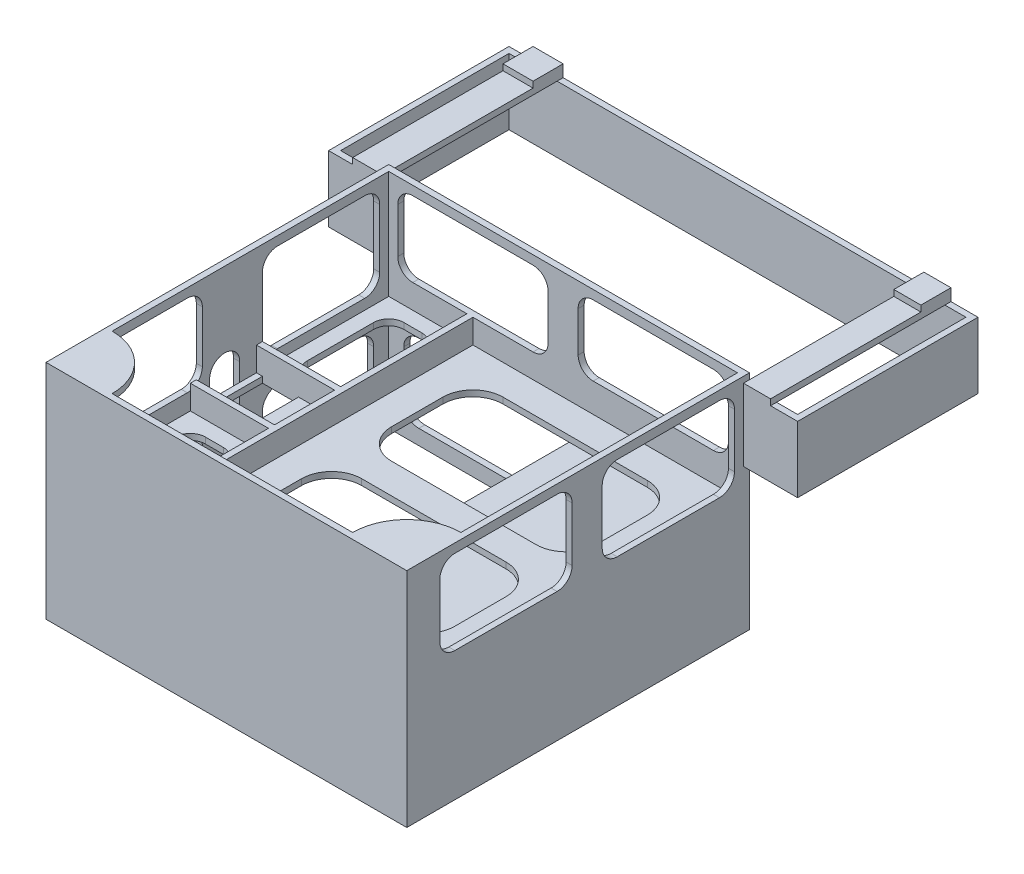
SolidWorks part; units mm, degrees
ref_plane "Front Plane" through (0, 0, 0) normal (0, 0, 1) x (1, 0, 0)
ref_plane "Top Plane" through (0, 0, 0) normal (0, 1, 0) x (1, 0, 0)
ref_plane "Right Plane" through (0, 0, 0) normal (1, 0, 0) x (0, 0, -1)
sketch "Sketch1" plane through (0, 0, 0) normal (0, 1, 0) x (1, 0, 0)
  line L1 (-113.8745, -60.9464) -> (-53.8745, -60.9464)
  line L2 (-113.8745, -60.9464) -> (-113.8745, -6.9464)
  line L3 (-113.8745, -6.9464) -> (-53.8745, -6.9464)
  line L4 (-53.8745, -60.9464) -> (-53.8745, -6.9464)
  dimension "D1" = 60
  dimension "D2" = 54
extrude "Boss-Extrude1" add sketch "Sketch1" along normal blind 38
sketch "Sketch2" plane through (0, 38, 0) normal (0, 1, 0) x (1, 0, 0)
  line L0 (-53.8745, -60.9464) -> (-53.8745, -6.9464) construction
  line L1 (-54.8745, -7.9464) -> (-98.8745, -7.9464)
  line L2 (-54.8745, -7.9464) -> (-54.8745, -59.9464)
  line L3 (-54.8745, -59.9464) -> (-98.8745, -59.9464)
  line L4 (-98.8745, -7.9464) -> (-98.8745, -59.9464)
  line L5 (-53.8745, -6.9464) -> (-113.8745, -6.9464) construction
  line L6 (-113.8745, -60.9464) -> (-53.8745, -60.9464) construction
  dimension "D1" = 1
  dimension "D2" = 1
  dimension "D3" = 1
  dimension "D4" = 44
extrude "Cut-Extrude1" cut sketch "Sketch2" against normal blind 19
sketch "Sketch3" plane through (0, 0, 0) normal (0, -1, 0) x (-1, 0, 0)
  line L0 (113.8745, -60.9464) -> (53.8745, -60.9464) construction
  line L1 (112.8745, -59.9464) -> (77.8745, -59.9464)
  line L2 (112.8745, -59.9464) -> (112.8745, -7.9464)
  line L3 (112.8745, -7.9464) -> (77.8745, -7.9464)
  line L4 (77.8745, -59.9464) -> (77.8745, -7.9464)
  line L5 (113.8745, -6.9464) -> (113.8745, -60.9464) construction
  line L6 (53.8745, -6.9464) -> (113.8745, -6.9464) construction
  dimension "D1" = 1
  dimension "D2" = 35
  dimension "D3" = 1
  dimension "D4" = 1
extrude "Cut-Extrude2" cut sketch "Sketch3" against normal blind 18
sketch "Sketch4" plane through (0, 18, 0) normal (0, -1, 0) x (-1, 0, 0)
  line L0 (77.8745, -59.9464) -> (112.8745, -59.9464) construction
  line L1 (111.8745, -39.9464) -> (105.8745, -39.9464)
  line L2 (111.8745, -39.9464) -> (111.8745, -29.9464)
  line L3 (111.8745, -29.9464) -> (105.8745, -29.9464)
  line L4 (105.8745, -39.9464) -> (105.8745, -29.9464)
  line L5 (112.8745, -7.9464) -> (77.8745, -7.9464) construction
  line L6 (112.8745, -59.9464) -> (112.8745, -7.9464) construction
  dimension "D1" = 20
  dimension "D2" = 22
  dimension "D3" = 1
  dimension "D4" = 6
extrude "Cut-Extrude3" cut sketch "Sketch4" against normal blind 38
sketch "Sketch5" plane through (0, 38, 0) normal (0, 1, 0) x (1, 0, 0)
  line L0 (-53.8745, -6.9464) -> (-113.8745, -6.9464) construction
  line L1 (-98.8745, -59.9464) -> (-112.8745, -59.9464)
  line L2 (-98.8745, -59.9464) -> (-98.8745, -7.9464)
  line L3 (-98.8745, -7.9464) -> (-112.8745, -7.9464)
  line L4 (-112.8745, -59.9464) -> (-112.8745, -7.9464)
  line L5 (-113.8745, -6.9464) -> (-113.8745, -60.9464) construction
  dimension "D1" = 1
  dimension "D2" = 1
extrude "Cut-Extrude5" cut sketch "Sketch5" against normal blind 15
sketch "Sketch6" plane through (0, 23, 0) normal (0, 1, 0) x (1, 0, 0)
  line L0 (-112.8745, -59.9464) -> (-98.8745, -59.9464) construction
  line L1 (-112.8745, -7.9464) -> (-99.8745, -7.9464)
  line L2 (-112.8745, -7.9464) -> (-112.8745, -59.9464)
  line L3 (-112.8745, -59.9464) -> (-99.8745, -59.9464)
  line L4 (-99.8745, -7.9464) -> (-99.8745, -59.9464)
  line L5 (-98.8745, -59.9464) -> (-98.8745, -7.9464) construction
  dimension "D1" = 1
extrude "Cut-Extrude6" cut sketch "Sketch6" against normal blind 4
sketch "Sketch8" plane through (0, 0, 0) normal (0, -1, 0) x (-1, 0, 0)
  line L0 (53.8745, -60.9464) -> (53.8745, -6.9464) construction
  line L1 (72.3745, -11.4464) -> (58.3745, -11.4464)
  line L2 (72.3745, -11.4464) -> (72.3745, -23.9464)
  line L3 (72.3745, -23.9464) -> (58.3745, -23.9464)
  line L4 (58.3745, -11.4464) -> (58.3745, -23.9464)
  line L6 (53.8745, -6.9464) -> (113.8745, -6.9464) construction
  dimension "D1" = 14
  dimension "D2" = 12.5
  dimension "D3" = 4.5
  dimension "D4" = 4.5
extrude "Cut-Extrude7" cut sketch "Sketch8" against normal blind 6
sketch "Sketch10" plane through (-72.3745, 0, 0) normal (1, 0, 0) x (0, 0, -1)
  line L0 (-11.4464, 6) -> (-11.4464, 0) construction
  line L1 (-23.9464, 6) -> (-11.4464, 6)
  line L2 (-23.9464, 6) -> (-23.9464, 1)
  line L3 (-23.9464, 1) -> (-11.4464, 1)
  line L4 (-11.4464, 6) -> (-11.4464, 1)
  line L5 (-23.9464, 0) -> (-11.4464, 0) construction
  dimension "D1" = 1
extrude "Cut-Extrude8" cut sketch "Sketch10" against normal blind 6
sketch "Sketch11" plane through (0, 0, 0) normal (0, -1, 0) x (1, 0, 0)
  line L0 (-113.8745, 60.9464) -> (-53.8745, 60.9464) construction
  line L1 (-68.3745, 50.9464) -> (-63.8745, 50.9464)
  line L2 (-68.3745, 50.9464) -> (-68.3745, 45.9464)
  line L3 (-68.3745, 45.9464) -> (-63.8745, 45.9464)
  line L4 (-63.8745, 50.9464) -> (-63.8745, 45.9464)
  line L5 (-53.8745, 60.9464) -> (-53.8745, 6.9464) construction
  dimension "D1" = 4.5
  dimension "D2" = 5
  dimension "D3" = 10
  dimension "D4" = 10
extrude "Cut-Extrude9" cut sketch "Sketch11" against normal blind 3
sketch "Sketch12" plane through (-68.3745, 0, 0) normal (1, 0, 0) x (0, 0, -1)
  line L0 (-50.9464, 3) -> (-50.9464, 0) construction
  line L1 (-45.9464, 3) -> (-50.9464, 3)
  line L2 (-45.9464, 3) -> (-45.9464, 1)
  line L3 (-45.9464, 1) -> (-50.9464, 1)
  line L4 (-50.9464, 3) -> (-50.9464, 1)
  line L5 (-50.9464, 0) -> (-45.9464, 0) construction
  dimension "D1" = 1
extrude "Cut-Extrude10" cut sketch "Sketch12" against normal blind 13
sketch "Sketch13" plane through (-113.8745, 0, 0) normal (-1, 0, 0) x (0, 0, 1)
  line L0 (35.233, 15) -> (35.233, 22) construction
  line L1 (32.733, 15) -> (32.733, 22)
  line L2 (37.733, 15) -> (37.733, 22)
  line L3 (59.9464, 18) -> (7.9464, 18) construction
  line L4 (39.9464, 19) -> (29.9464, 19) construction
  arc A0 (32.733, 15) -> (37.733, 15) centre (35.233, 15) ccw
  arc A1 (37.733, 22) -> (32.733, 22) centre (35.233, 22) ccw
  point P2 (35.233, 18.5)
  dimension "D1" = 3
  dimension "D2" = 3
  dimension "D3" = 2.5
extrude "Cut-Extrude11" cut sketch "Sketch13" against normal blind 1
sketch "Sketch14" plane through (0, 19, 0) normal (0, 1, 0) x (1, 0, 0)
  line L0 (-99.8745, -59.9464) -> (-99.8745, -7.9464) construction
  line L1 (-112.8745, -40.9464) -> (-99.8745, -40.9464)
  line L2 (-112.8745, -40.9464) -> (-112.8745, -39.9464)
  line L3 (-112.8745, -39.9464) -> (-99.8745, -39.9464)
  line L4 (-99.8745, -40.9464) -> (-99.8745, -39.9464)
  line L5 (-112.8745, -37.733) -> (-112.8745, -59.9464) construction
  line L6 (-105.8745, -39.9464) -> (-111.8745, -39.9464) construction
  dimension "D1" = 0
  dimension "D2" = 1
  dimension "D3" = 0
extrude "Boss-Extrude2" add sketch "Sketch14" along normal blind 4
sketch "Sketch15" plane through (0, 19, 0) normal (0, 1, 0) x (1, 0, 0)
  line L0 (-112.8745, -7.9464) -> (-112.8745, -32.733) construction
  line L1 (-112.8745, -29.9464) -> (-99.8745, -29.9464)
  line L2 (-112.8745, -29.9464) -> (-112.8745, -28.9464)
  line L3 (-112.8745, -28.9464) -> (-99.8745, -28.9464)
  line L4 (-99.8745, -29.9464) -> (-99.8745, -28.9464)
  line L5 (-99.8745, -39.9464) -> (-99.8745, -7.9464) construction
  line L6 (-111.8745, -29.9464) -> (-105.8745, -29.9464) construction
  dimension "D1" = 0
  dimension "D2" = 1
extrude "Boss-Extrude3" add sketch "Sketch15" along normal blind 4
sketch "Sketch16" plane through (0, 19, 0) normal (0, 1, 0) x (1, 0, 0)
  line L0 (-98.8745, -59.9464) -> (-54.8745, -59.9464) construction
  line L1 (-64.8745, -54.9464) -> (-88.8745, -54.9464)
  line L2 (-59.8745, -49.9464) -> (-59.8745, -41.4464)
  line L3 (-64.8745, -36.4464) -> (-88.8745, -36.4464)
  line L4 (-93.8745, -49.9464) -> (-93.8745, -41.4464)
  line L5 (-88.8745, -31.4464) -> (-64.8745, -31.4464)
  line L6 (-93.8745, -26.4464) -> (-93.8745, -17.9464)
  line L7 (-88.8745, -12.9464) -> (-64.8745, -12.9464)
  line L8 (-59.8745, -26.4464) -> (-59.8745, -17.9464)
  line L9 (-54.8745, -59.9464) -> (-54.8745, -7.9464) construction
  line L10 (-98.8745, -7.9464) -> (-98.8745, -59.9464) construction
  line L11 (-54.8745, -7.9464) -> (-98.8745, -7.9464) construction
  arc A0 (-64.8745, -31.4464) -> (-59.8745, -26.4464) centre (-64.8745, -26.4464) ccw
  arc A1 (-64.8745, -12.9464) -> (-59.8745, -17.9464) centre (-64.8745, -17.9464) cw
  arc A2 (-93.8745, -17.9464) -> (-88.8745, -12.9464) centre (-88.8745, -17.9464) cw
  arc A3 (-88.8745, -31.4464) -> (-93.8745, -26.4464) centre (-88.8745, -26.4464) cw
  arc A4 (-88.8745, -54.9464) -> (-93.8745, -49.9464) centre (-88.8745, -49.9464) cw
  arc A5 (-88.8745, -36.4464) -> (-93.8745, -41.4464) centre (-88.8745, -41.4464) ccw
  arc A6 (-59.8745, -41.4464) -> (-64.8745, -36.4464) centre (-64.8745, -41.4464) ccw
  arc A7 (-64.8745, -54.9464) -> (-59.8745, -49.9464) centre (-64.8745, -49.9464) ccw
  point P22 (-93.8745, -12.9464)
  point P25 (-93.8745, -31.4464)
  dimension "D9" = 5
  dimension "D1" = 5
  dimension "D2" = 5
  dimension "D3" = 5
  dimension "D4" = 5
  dimension "D5" = 5
  dimension "D6" = 5
  dimension "D7" = 5
  dimension "D8" = 18.5
extrude "Cut-Extrude12" cut sketch "Sketch16" against normal blind 1
sketch "Sketch17" plane through (0, 19, 0) normal (0, 1, 0) x (1, 0, 0)
  line L0 (-112.8745, -40.9464) -> (-112.8745, -59.9464) construction
  line L1 (-104.8745, -57.4464) -> (-107.8745, -57.4464)
  line L2 (-102.3745, -54.9464) -> (-102.3745, -45.9464)
  line L3 (-104.8745, -43.4464) -> (-107.8745, -43.4464)
  line L4 (-110.3745, -54.9464) -> (-110.3745, -45.9464)
  line L5 (-104.8745, -26.4464) -> (-107.8745, -26.4464)
  line L6 (-102.3745, -23.9464) -> (-102.3745, -12.9464)
  line L7 (-104.8745, -10.4464) -> (-107.8745, -10.4464)
  line L8 (-110.3745, -23.9464) -> (-110.3745, -12.9464)
  line L9 (-99.8745, -59.9464) -> (-99.8745, -40.9464) construction
  line L10 (-112.8745, -40.9464) -> (-99.8745, -40.9464) construction
  line L11 (-112.8745, -59.9464) -> (-99.8745, -59.9464) construction
  line L12 (-99.8745, -28.9464) -> (-112.8745, -28.9464) construction
  line L13 (-112.8745, -7.9464) -> (-112.8745, -28.9464) construction
  line L14 (-99.8745, -28.9464) -> (-99.8745, -7.9464) construction
  line L15 (-99.8745, -7.9464) -> (-112.8745, -7.9464) construction
  arc A0 (-102.3745, -12.9464) -> (-104.8745, -10.4464) centre (-104.8745, -12.9464) ccw
  arc A1 (-107.8745, -10.4464) -> (-110.3745, -12.9464) centre (-107.8745, -12.9464) ccw
  arc A2 (-107.8745, -26.4464) -> (-110.3745, -23.9464) centre (-107.8745, -23.9464) cw
  arc A3 (-104.8745, -26.4464) -> (-102.3745, -23.9464) centre (-104.8745, -23.9464) ccw
  arc A4 (-102.3745, -45.9464) -> (-104.8745, -43.4464) centre (-104.8745, -45.9464) ccw
  arc A5 (-107.8745, -43.4464) -> (-110.3745, -45.9464) centre (-107.8745, -45.9464) ccw
  arc A6 (-107.8745, -57.4464) -> (-110.3745, -54.9464) centre (-107.8745, -54.9464) cw
  arc A7 (-104.8745, -57.4464) -> (-102.3745, -54.9464) centre (-104.8745, -54.9464) ccw
  dimension "D9" = 2.5
  dimension "D1" = 2.5
  dimension "D2" = 2.5
  dimension "D3" = 2.5
  dimension "D4" = 2.5
  dimension "D5" = 2.5
  dimension "D6" = 2.5
  dimension "D7" = 2.5
  dimension "D8" = 2.5
extrude "Cut-Extrude13" cut sketch "Sketch17" against normal blind 1
sketch "Sketch18" plane through (-53.8745, 0, 0) normal (1, 0, 0) x (0, 0, -1)
  line L0 (-60.9464, 38) -> (-6.9464, 38) construction
  line L1 (-55.9464, 35.5) -> (-38.9464, 35.5)
  line L2 (-58.4464, 33) -> (-58.4464, 24)
  line L3 (-55.9464, 21.5) -> (-38.9464, 21.5)
  line L4 (-36.4464, 33) -> (-36.4464, 24)
  line L5 (-28.9464, 35.5) -> (-11.9464, 35.5)
  line L6 (-31.4464, 33) -> (-31.4464, 24)
  line L7 (-28.9464, 21.5) -> (-11.9464, 21.5)
  line L8 (-9.4464, 33) -> (-9.4464, 24)
  line L9 (-60.9464, 38) -> (-60.9464, 0) construction
  line L10 (-6.9464, 38) -> (-6.9464, 0) construction
  line L11 (-59.9464, 19) -> (-7.9464, 19) construction
  arc A0 (-31.4464, 24) -> (-28.9464, 21.5) centre (-28.9464, 24) ccw
  arc A1 (-11.9464, 21.5) -> (-9.4464, 24) centre (-11.9464, 24) ccw
  arc A2 (-11.9464, 35.5) -> (-9.4464, 33) centre (-11.9464, 33) cw
  arc A3 (-28.9464, 35.5) -> (-31.4464, 33) centre (-28.9464, 33) ccw
  arc A4 (-58.4464, 24) -> (-55.9464, 21.5) centre (-55.9464, 24) ccw
  arc A5 (-38.9464, 21.5) -> (-36.4464, 24) centre (-38.9464, 24) ccw
  arc A6 (-38.9464, 35.5) -> (-36.4464, 33) centre (-38.9464, 33) cw
  arc A7 (-55.9464, 35.5) -> (-58.4464, 33) centre (-55.9464, 33) ccw
  point P26 (-58.4464, 21.5)
  point P29 (-36.4464, 21.5)
  dimension "D9" = 2.5
  dimension "D1" = 2.5
  dimension "D2" = 2.5
  dimension "D3" = 2.5
  dimension "D4" = 2.5
  dimension "D5" = 5
  dimension "D6" = 22
  dimension "D7" = 2.5
  dimension "D8" = 2.5
extrude "Cut-Extrude14" cut sketch "Sketch18" against normal blind 1
sketch "Sketch19" plane through (0, 0, 6.9464) normal (0, 0, -1) x (-1, 0, 0)
  line L0 (53.8745, 38) -> (113.8745, 38) construction
  line L1 (58.8745, 35.5) -> (78.8745, 35.5)
  line L2 (56.3745, 33) -> (56.3745, 26.3041)
  line L3 (58.8745, 23.8041) -> (78.8745, 23.8041)
  line L4 (81.3745, 33) -> (81.3745, 26.3041)
  line L5 (88.8745, 35.5) -> (108.8745, 35.5)
  line L6 (86.3745, 33) -> (86.3745, 25.5)
  line L7 (88.8745, 23) -> (108.8745, 23)
  line L8 (111.3745, 33) -> (111.3745, 25.5)
  line L9 (113.8745, 38) -> (113.8745, 0) construction
  line L10 (53.8745, 38) -> (53.8745, 0) construction
  arc A0 (108.8745, 23) -> (111.3745, 25.5) centre (108.8745, 25.5) ccw
  arc A1 (108.8745, 35.5) -> (111.3745, 33) centre (108.8745, 33) cw
  arc A2 (88.8745, 35.5) -> (86.3745, 33) centre (88.8745, 33) ccw
  arc A3 (86.3745, 25.5) -> (88.8745, 23) centre (88.8745, 25.5) ccw
  arc A4 (78.8745, 23.8041) -> (81.3745, 26.3041) centre (78.8745, 26.3041) ccw
  arc A5 (78.8745, 35.5) -> (81.3745, 33) centre (78.8745, 33) cw
  arc A6 (56.3745, 26.3041) -> (58.8745, 23.8041) centre (58.8745, 26.3041) ccw
  arc A7 (58.8745, 35.5) -> (56.3745, 33) centre (58.8745, 33) ccw
  point P17 (111.3745, 23)
  point P24 (86.3745, 23)
  dimension "D8" = 2.5
  dimension "D1" = 2.5
  dimension "D2" = 2.5
  dimension "D3" = 2.5
  dimension "D4" = 2.5
  dimension "D5" = 5
  dimension "D6" = 25
  dimension "D7" = 0
extrude "Cut-Extrude15" cut sketch "Sketch19" against normal blind 60
sketch "Sketch20" plane through (-113.8745, 0, 0) normal (-1, 0, 0) x (0, 0, 1)
  line L0 (59.9464, 38) -> (7.9464, 38) construction
  line L1 (11.9464, 35.5) -> (26.4464, 35.5)
  line L2 (9.4464, 33) -> (9.4464, 23.222)
  line L3 (11.9464, 20.722) -> (26.4464, 20.722)
  line L4 (28.9464, 33) -> (28.9464, 23.222)
  line L5 (41.4464, 35.5) -> (55.9464, 35.5)
  line L6 (38.9464, 33) -> (38.9464, 24.3756)
  line L7 (41.4464, 21.8756) -> (55.9464, 21.8756)
  line L8 (58.4464, 33) -> (58.4464, 24.3756)
  line L9 (6.9464, 38) -> (6.9464, 0) construction
  line L10 (60.9464, 38) -> (60.9464, 0) construction
  line L11 (6.9464, 38) -> (60.9464, 38) construction
  arc A0 (38.9464, 24.3756) -> (41.4464, 21.8756) centre (41.4464, 24.3756) ccw
  arc A1 (55.9464, 21.8756) -> (58.4464, 24.3756) centre (55.9464, 24.3756) ccw
  arc A2 (55.9464, 35.5) -> (58.4464, 33) centre (55.9464, 33) cw
  arc A3 (41.4464, 35.5) -> (38.9464, 33) centre (41.4464, 33) ccw
  arc A4 (9.4464, 23.222) -> (11.9464, 20.722) centre (11.9464, 23.222) ccw
  arc A5 (26.4464, 20.722) -> (28.9464, 23.222) centre (26.4464, 23.222) ccw
  arc A6 (26.4464, 35.5) -> (28.9464, 33) centre (26.4464, 33) cw
  arc A7 (11.9464, 35.5) -> (9.4464, 33) centre (11.9464, 33) ccw
  point P18 (38.9464, 21.8756)
  point P21 (58.4464, 21.8756)
  dimension "D7" = 2.5
  dimension "D1" = 2.5
  dimension "D2" = 2.5
  dimension "D3" = 10
  dimension "D4" = 2.5
  dimension "D5" = 2.5
  dimension "D6" = 19.5
extrude "Cut-Extrude16" cut sketch "Sketch20" against normal blind 1
sketch "Sketch21" plane through (0, 0, 59.9464) normal (0, 0, -1) x (-1, 0, 0)
  line L0 (77.8745, 0) -> (112.8745, 0) construction
  line L1 (107.8745, 2.5) -> (82.8745, 2.5)
  line L2 (110.3745, 5) -> (110.3745, 13)
  line L3 (107.8745, 15.5) -> (82.8745, 15.5)
  line L4 (80.3745, 5) -> (80.3745, 13)
  line L5 (77.8745, 18) -> (77.8745, 0) construction
  line L6 (112.8745, 18) -> (112.8745, 0) construction
  line L7 (77.8745, 18) -> (112.8745, 18) construction
  arc A0 (110.3745, 13) -> (107.8745, 15.5) centre (107.8745, 13) ccw
  arc A1 (82.8745, 15.5) -> (80.3745, 13) centre (82.8745, 13) ccw
  arc A2 (82.8745, 2.5) -> (80.3745, 5) centre (82.8745, 5) cw
  arc A3 (107.8745, 2.5) -> (110.3745, 5) centre (107.8745, 5) ccw
  dimension "D5" = 2.5
  dimension "D1" = 2.5
  dimension "D2" = 2.5
  dimension "D3" = 2.5
  dimension "D4" = 2.5
extrude "Cut-Extrude17" cut sketch "Sketch21" along normal blind 100 and the other way blind 10
sketch "Sketch22" plane through (-112.8745, 0, 0) normal (1, 0, 0) x (0, 0, -1)
  line L0 (-59.9464, 0) -> (-7.9464, 0) construction
  line L1 (-12.9464, 2.5) -> (-26.4464, 2.5)
  line L2 (-10.4464, 5) -> (-10.4464, 13)
  line L3 (-12.9464, 15.5) -> (-26.4464, 15.5)
  line L4 (-28.9464, 5) -> (-28.9464, 13)
  line L5 (-41.4464, 2.5) -> (-54.9464, 2.5)
  line L6 (-38.9464, 5) -> (-38.9464, 13)
  line L7 (-41.4464, 15.5) -> (-54.9464, 15.5)
  line L8 (-57.4464, 5) -> (-57.4464, 13)
  line L9 (-7.9464, 18) -> (-7.9464, 0) construction
  line L10 (-32.733, 18) -> (-7.9464, 18) construction
  line L11 (-59.9464, 18) -> (-37.733, 18) construction
  line L12 (-59.9464, 18) -> (-59.9464, 0) construction
  arc A0 (-38.9464, 13) -> (-41.4464, 15.5) centre (-41.4464, 13) ccw
  arc A1 (-54.9464, 15.5) -> (-57.4464, 13) centre (-54.9464, 13) ccw
  arc A2 (-54.9464, 2.5) -> (-57.4464, 5) centre (-54.9464, 5) cw
  arc A3 (-41.4464, 2.5) -> (-38.9464, 5) centre (-41.4464, 5) ccw
  arc A4 (-26.4464, 2.5) -> (-28.9464, 5) centre (-26.4464, 5) cw
  arc A5 (-26.4464, 15.5) -> (-28.9464, 13) centre (-26.4464, 13) ccw
  arc A6 (-10.4464, 13) -> (-12.9464, 15.5) centre (-12.9464, 13) ccw
  arc A7 (-12.9464, 2.5) -> (-10.4464, 5) centre (-12.9464, 5) ccw
  point P30 (-28.9464, 15.5)
  point P33 (-10.4464, 15.5)
  dimension "D9" = 2.5
  dimension "D1" = 2.5
  dimension "D2" = 10
  dimension "D3" = 2.5
  dimension "D4" = 2.5
  dimension "D5" = 2.5
  dimension "D6" = 2.5
  dimension "D7" = 2.5
  dimension "D8" = 18.5
extrude "Cut-Extrude18" cut sketch "Sketch22" against normal blind 10
sketch "Sketch23" plane through (0, 38, 0) normal (0, 1, 0) x (1, 0, 0)
  line L1 (-112.8745, -59.9464) -> (-54.8745, -59.9464)
  line L2 (-112.8745, -59.9464) -> (-112.8745, -7.9464)
  line L3 (-112.8745, -7.9464) -> (-54.8745, -7.9464)
  line L4 (-54.8745, -59.9464) -> (-54.8745, -7.9464)
extrude "Boss-Extrude4" add sketch "Sketch23" against normal blind 1
sketch "Sketch24" plane through (0, 38, 0) normal (0, 1, 0) x (1, 0, 0)
  line L0 (-113.8745, -6.9464) -> (-113.8745, -60.9464) construction
  line L1 (-113.8745, -50.9464) -> (-53.8745, -50.9464)
  line L2 (-113.8745, -50.9464) -> (-113.8745, -16.9464)
  line L3 (-113.8745, -16.9464) -> (-53.8745, -16.9464)
  line L4 (-53.8745, -50.9464) -> (-53.8745, -16.9464)
  line L5 (-53.8745, -60.9464) -> (-53.8745, -6.9464) construction
  line L6 (-53.8745, -6.9464) -> (-113.8745, -6.9464) construction
  line L7 (-103.8745, -6.9464) -> (-63.8745, -6.9464)
  line L8 (-103.8745, -6.9464) -> (-103.8745, -60.9464)
  line L9 (-103.8745, -60.9464) -> (-63.8745, -60.9464)
  line L10 (-63.8745, -6.9464) -> (-63.8745, -60.9464)
  line L11 (-113.8745, -60.9464) -> (-53.8745, -60.9464) construction
  line L12 (-58.8745, -60.9464) -> (-56.3745, -60.9464) construction
  line M5 (-113.8745, -6.9464) -> (-113.8745, -60.9464)
  line M6 (-113.8745, -60.9464) -> (-53.8745, -60.9464)
  line M7 (-53.8745, -60.9464) -> (-53.8745, -6.9464)
  line M8 (-53.8745, -6.9464) -> (-113.8745, -6.9464)
  dimension "D1" = 10
  dimension "D2" = 10
  dimension "D3" = 10
  dimension "D4" = 10
extrude "Cut-Extrude20" cut sketch "Sketch24" against normal blind 1 contours L10 L1 L8 M6 | L3 L10 L1 M7 | L10 L8 L3 M8 | L10 L3 L8 L1 | L8 L3 L1 M5
fillet "Fillet1" radius 9 3 edges at (-103.8745, 37, 55.4464) (-108.3745, 37, 50.9464) (-103.8745, 37.5, 50.9464)
fillet "Fillet2" radius 9 3 edges at (-63.8745, 37, 12.4464) (-59.3745, 37, 16.9464) (-63.8745, 37.5, 16.9464)
fillet "Fillet3" radius 9 3 edges at (-63.8745, 37, 55.4464) (-63.8745, 37.5, 50.9464) (-59.3745, 37, 50.9464)
fillet "Fillet4" radius 9 3 edges at (-108.3745, 37, 16.9464) (-103.8745, 37, 12.4464) (-103.8745, 37.5, 16.9464)
sketch "Sketch27" plane through (0, 0, 6.9464) normal (0, 0, -1) x (-1, 0, 0)
  line L0 (53.8745, 38) -> (53.8745, 0) construction
  line L1 (53.8745, 24) -> (43.8745, 24)
  line L2 (53.8745, 24) -> (53.8745, 35)
  line L3 (53.8745, 35) -> (43.8745, 35)
  line L4 (43.8745, 24) -> (43.8745, 35)
  line L5 (113.8745, 38) -> (113.8745, 0) construction
  line L6 (113.8745, 24) -> (123.8745, 24)
  line L7 (113.8745, 24) -> (113.8745, 35)
  line L8 (113.8745, 35) -> (123.8745, 35)
  line L9 (123.8745, 24) -> (123.8745, 35)
  line L10 (63.8745, 37) -> (103.8745, 37) construction
  dimension "D1" = 2
  dimension "D2" = 2
  dimension "D3" = 80
  dimension "D4" = 10
  dimension "D5" = 11
  dimension "D6" = 11
extrude "Boss-Extrude10" add sketch "Sketch27" against normal blind 1
sketch "Sketch31" plane through (0, 0, 6.9464) normal (0, 0, -1) x (-1, 0, 0)
  line L0 (43.8745, 24) -> (53.8745, 24) construction
  line L1 (43.8745, 24) -> (44.8745, 24)
  line L2 (43.8745, 24) -> (43.8745, 35)
  line L3 (43.8745, 35) -> (44.8745, 35)
  line L4 (44.8745, 24) -> (44.8745, 35)
  line L5 (53.8745, 35) -> (43.8745, 35) construction
  line L6 (123.8745, 35) -> (113.8745, 35) construction
  line L7 (122.8745, 35) -> (123.8745, 35)
  line L8 (122.8745, 35) -> (122.8745, 24)
  line L9 (122.8745, 24) -> (123.8745, 24)
  line L10 (123.8745, 35) -> (123.8745, 24)
  dimension "D1" = 1
  dimension "D2" = 1
extrude "Boss-Extrude12" add sketch "Sketch31" along normal blind 29
sketch "Sketch33" plane through (-44.8745, 0, 0) normal (-1, 0, 0) x (0, 0, 1)
  line L0 (-22.0536, 24) -> (6.9464, 24) construction
  line L1 (-22.0536, 35) -> (-21.0536, 35)
  line L2 (-22.0536, 35) -> (-22.0536, 24)
  line L3 (-22.0536, 24) -> (-21.0536, 24)
  line L4 (-21.0536, 35) -> (-21.0536, 24)
  dimension "D1" = 1
extrude "Boss-Extrude13" add sketch "Sketch33" along normal blind 78
sketch "Sketch34" plane through (0, 35, 0) normal (0, 1, 0) x (1, 0, 0)
  line L0 (-123.8745, -7.9464) -> (-113.8745, -7.9464) construction
  line L1 (-123.8745, 22.0536) -> (-43.8745, 22.0536) construction
  line L2 (-118.8745, -7.9464) -> (-113.8745, -7.9464)
  line L3 (-118.8745, -7.9464) -> (-118.8745, 22.0536)
  line L4 (-118.8745, 22.0536) -> (-113.8745, 22.0536)
  line L5 (-113.8745, -7.9464) -> (-113.8745, 22.0536)
  line L7 (-53.8745, -7.9464) -> (-49.3745, -7.9464)
  line L8 (-53.8745, -7.9464) -> (-53.8745, 22.0536)
  line L9 (-53.8745, 22.0536) -> (-49.3745, 22.0536)
  line L10 (-49.3745, -7.9464) -> (-49.3745, 22.0536)
extrude "Boss-Extrude14" add sketch "Sketch34" along normal blind 1
sketch "Sketch35" plane through (-122.8745, 0, 0) normal (1, 0, 0) x (0, 0, -1)
  line L0 (21.0536, 24) -> (-6.9464, 24) construction
  line L1 (21.0536, 24) -> (-6.9464, 24)
  line L2 (21.0536, 24) -> (21.0536, 35)
  line L3 (21.0536, 35) -> (-6.9464, 35)
  line L4 (-6.9464, 24) -> (-6.9464, 35)
extrude "Boss-Extrude15" add sketch "Sketch35" along normal blind 1
sketch "Sketch37" plane through (-123.8745, 0, 0) normal (-1, 0, 0) x (0, 0, 1)
  line L1 (7.9464, 35) -> (-22.0536, 35)
  line L2 (7.9464, 35) -> (7.9464, 24)
  line L3 (7.9464, 24) -> (-22.0536, 24)
  line L4 (-22.0536, 35) -> (-22.0536, 24)
  point P4 (-10.4832, 37.0116)
extrude "Cut-Extrude21" cut sketch "Sketch37" against normal blind 1
sketch "Sketch38" plane through (-44.8745, 0, 0) normal (-1, 0, 0) x (0, 0, 1)
  line L1 (6.9464, 35) -> (-21.0536, 35)
  line L2 (6.9464, 35) -> (6.9464, 24)
  line L3 (6.9464, 24) -> (-21.0536, 24)
  line L4 (-21.0536, 35) -> (-21.0536, 24)
extrude "Boss-Extrude16" add sketch "Sketch38" along normal blind 1
sketch "Sketch39" plane through (-43.8745, 0, 0) normal (1, 0, 0) x (0, 0, -1)
  line L1 (-7.9464, 24) -> (22.0536, 24)
  line L2 (-7.9464, 24) -> (-7.9464, 35)
  line L3 (-7.9464, 35) -> (22.0536, 35)
  line L4 (22.0536, 24) -> (22.0536, 35)
  point P4 (10.6616, 17.0387)
extrude "Cut-Extrude22" cut sketch "Sketch39" against normal blind 1
sketch "Sketch40" plane through (0, 0, 60.9464) normal (0, 0, 1) x (1, 0, 0)
  line L0 (-113.8745, 38) -> (-113.8745, 0) construction
  line L1 (-53.8745, 0) -> (-113.8745, 0)
  line L2 (-53.8745, 0) -> (-53.8745, 37)
  line L3 (-53.8745, 37) -> (-113.8745, 37)
  line L4 (-113.8745, 0) -> (-113.8745, 37)
  dimension "D1" = 37
extrude "Boss-Extrude17" add sketch "Sketch40" along normal blind 3
sketch "Sketch41" plane through (0, 0, 59.9464) normal (0, 0, -1) x (-1, 0, 0)
  line L1 (112.8745, 0) -> (77.8745, 0)
  line L2 (112.8745, 0) -> (112.8745, 18)
  line L3 (112.8745, 18) -> (77.8745, 18)
  line L4 (77.8745, 0) -> (77.8745, 18)
  point P4 (75.1365, 25.7269)
extrude "Cut-Extrude23" cut sketch "Sketch41" against normal blind 3
sketch "Sketch42" plane through (0, 0, 59.9464) normal (0, 0, -1) x (-1, 0, 0)
  line L0 (98.8745, 19) -> (54.8745, 19) construction
  line L1 (98.8745, 19) -> (54.8745, 19)
  line L2 (98.8745, 19) -> (98.8745, 37)
  line L3 (98.8745, 37) -> (54.8745, 37)
  line L4 (54.8745, 19) -> (54.8745, 37)
  line L5 (54.8745, 19) -> (54.8745, 37) construction
  point P8 (53.8849, 38.6439)
  point P9 (85.8975, 35.987)
extrude "Cut-Extrude24" cut sketch "Sketch42" against normal blind 3
sketch "Sketch44" plane through (0, 0, 59.9464) normal (0, 0, -1) x (-1, 0, 0)
  line L0 (103.8745, 37) -> (98.8745, 37) construction
  line L1 (112.8745, 19) -> (99.8745, 19)
  line L2 (112.8745, 19) -> (112.8745, 37)
  line L3 (112.8745, 37) -> (99.8745, 37)
  line L4 (99.8745, 19) -> (99.8745, 37)
  point P7 (100.7339, 25.4341)
  dimension "D1" = 13
extrude "Cut-Extrude25" cut sketch "Sketch44" against normal blind 3
sketch "Sketch45" plane through (-98.8745, 0, 0) normal (1, 0, 0) x (0, 0, -1)
  line L0 (-62.9464, 37) -> (-59.9464, 37) construction
  line L1 (-62.9464, 37) -> (-59.9464, 37)
  line L2 (-62.9464, 37) -> (-62.9464, 23)
  line L3 (-62.9464, 23) -> (-59.9464, 23)
  line L4 (-59.9464, 37) -> (-59.9464, 23)
  line L5 (-60.9464, 23) -> (-7.9464, 23) construction
  point P8 (-55.7959, 40.5595)
extrude "Cut-Extrude26" cut sketch "Sketch45" against normal blind 3
sketch "Sketch47" plane through (0, 38, 0) normal (0, 1, 0) x (1, 0, 0)
  line L1 (-113.8745, -6.9464) -> (-53.8745, -6.9464)
  line L2 (-113.8745, -6.9464) -> (-113.8745, -16.9464)
  line L3 (-113.8745, -16.9464) -> (-53.8745, -16.9464)
  line L4 (-53.8745, -6.9464) -> (-53.8745, -16.9464)
  point P4 (-59.3076, -20.2299)
extrude "Cut-Extrude27" cut sketch "Sketch47" against normal blind 1
sketch "Sketch48" plane through (0, 38, 0) normal (0, 1, 0) x (1, 0, 0)
  line L1 (-113.8745, -60.9464) -> (-53.8745, -60.9464)
  line L2 (-113.8745, -60.9464) -> (-113.8745, -50.9464)
  line L3 (-113.8745, -50.9464) -> (-53.8745, -50.9464)
  line L4 (-53.8745, -60.9464) -> (-53.8745, -50.9464)
  point P4 (-62.7142, -56.495)
extrude "Cut-Extrude28" cut sketch "Sketch48" against normal blind 1
sketch "Sketch49" plane through (0, 37, 0) normal (0, 1, 0) x (1, 0, 0)
  line L0 (-53.8745, -63.9464) -> (-53.8745, -6.9464) construction
  line L1 (-113.8745, -63.9464) -> (-53.8745, -63.9464)
  line L2 (-113.8745, -63.9464) -> (-113.8745, -53.9464)
  line L3 (-113.8745, -53.9464) -> (-53.8745, -53.9464)
  line L4 (-53.8745, -63.9464) -> (-53.8745, -53.9464)
  point P7 (-57.1074, -55.3344)
  dimension "D1" = 10
extrude "Boss-Extrude18" add sketch "Sketch49" against normal blind 1
sketch "Sketch50" plane through (0, 37, 0) normal (0, 1, 0) x (1, 0, 0)
  line L0 (-54.8745, -53.9464) -> (-112.8745, -53.9464) construction
  line L1 (-103.8745, -53.9464) -> (-63.8745, -53.9464)
  line L2 (-103.8745, -53.9464) -> (-103.8745, -62.9464)
  line L3 (-103.8745, -62.9464) -> (-63.8745, -62.9464)
  line L4 (-63.8745, -53.9464) -> (-63.8745, -62.9464)
  line L5 (-53.8745, -63.9464) -> (-113.8745, -63.9464) construction
  line L6 (-53.8745, -63.9464) -> (-53.8745, -6.9464) construction
  line L7 (-113.8745, -6.9464) -> (-113.8745, -63.9464) construction
  dimension "D1" = 1
  dimension "D2" = 10
  dimension "D3" = 10
extrude "Cut-Extrude29" cut sketch "Sketch50" against normal blind 1 contours L2 L1 L4 L3
fillet "Fillet5" radius 9 5 edges at (-108.3745, 36, 53.9464) (-108.3745, 37, 53.9464) (-103.8745, 36, 58.4464) (-103.8745, 36.5, 53.9464) (-103.8745, 37, 58.4464)
fillet "Fillet6" radius 9 5 edges at (-59.3745, 36, 53.9464) (-59.3745, 37, 53.9464) (-63.8745, 37, 58.4464) (-63.8745, 36.5, 53.9464) (-63.8745, 36, 58.4464)
sketch "Sketch51" plane through (0, 36, 0) normal (0, 1, 0) x (1, 0, 0)
  line L0 (-113.8745, 22.0536) -> (-118.8745, 22.0536) construction
  line L1 (-113.8745, 22.0536) -> (-118.8745, 22.0536)
  line L2 (-113.8745, 22.0536) -> (-113.8745, 17.0536)
  line L3 (-113.8745, 17.0536) -> (-118.8745, 17.0536)
  line L4 (-118.8745, 22.0536) -> (-118.8745, 17.0536)
  line L5 (-118.8745, 22.0536) -> (-118.8745, -7.9464) construction
  line L6 (-53.8745, 22.0536) -> (-53.8745, -6.9464) construction
  line L7 (-49.3745, 22.0536) -> (-53.8745, 22.0536)
  line L8 (-49.3745, 22.0536) -> (-49.3745, 17.0536)
  line L9 (-49.3745, 17.0536) -> (-53.8745, 17.0536)
  line L10 (-53.8745, 22.0536) -> (-53.8745, 17.0536)
  dimension "D1" = 5
extrude "Boss-Extrude19" add sketch "Sketch51" along normal blind 1
